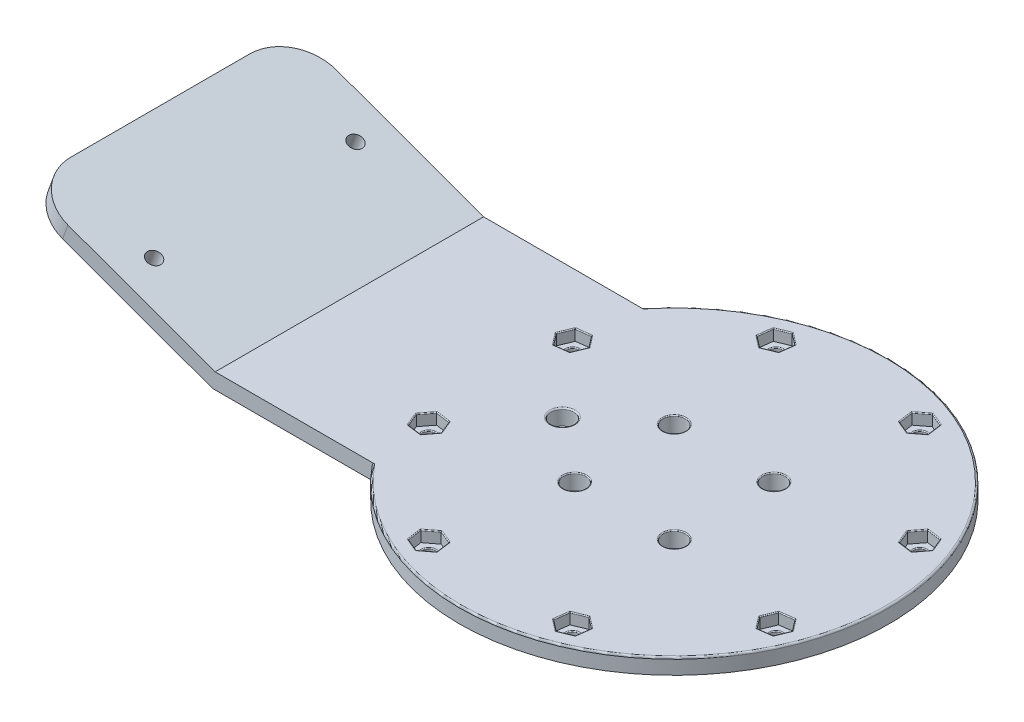
SolidWorks part; units mm, degrees
ref_plane "前视基准面" through (0, 0, 0) normal (0, 0, 1) x (1, 0, 0)
ref_plane "上视基准面" through (0, 0, 0) normal (0, 1, 0) x (1, 0, 0)
ref_plane "右视基准面" through (0, 0, 0) normal (1, 0, 0) x (0, 0, -1)
other "Configuration Table"
sketch "草图1" plane through (0, 0, 0) normal (0, 0, 1) x (1, 0, 0)
  line L0 (48, 6) -> (0, 6)
  line L1 (0, 6) -> (0, 0)
  line L2 (0, 0) -> (48, 0)
  line L3 (48, 0) -> (48, 6)
  line L4 (0, 6) -> (0, 0) construction
revolve "旋转1" add sketch "草图1" angle 360 about L4 reverse direction yes
sketch "草图2" plane through (0, 6, 0) normal (0, 1, 0) x (-1, 0, 0)
  line L0 (42.0084, 15.6507) -> (40.7712, 18.6377)
  line L1 (40.7712, 18.6377) -> (37.5657, 19.0598)
  line L2 (37.5657, 19.0598) -> (35.5974, 16.4947)
  line L3 (35.5974, 16.4947) -> (36.8347, 13.5077)
  line L4 (36.8347, 13.5077) -> (40.0402, 13.0857)
  line L5 (40.0402, 13.0857) -> (42.0084, 15.6507)
extrude "切除-拉伸1" cut sketch "草图2" against normal blind 2.5
sketch "草图3" plane through (0, 6, 0) normal (0, 1, 0) x (-1, 0, 0)
  line L0 (18.6377, 40.7712) -> (15.6507, 42.0084)
  line L1 (15.6507, 42.0084) -> (13.0857, 40.0402)
  line L2 (13.0857, 40.0402) -> (13.5077, 36.8347)
  line L3 (13.5077, 36.8347) -> (16.4947, 35.5974)
  line L4 (16.4947, 35.5974) -> (19.0598, 37.5657)
  line L5 (19.0598, 37.5657) -> (18.6377, 40.7712)
extrude "切除-拉伸2" cut sketch "草图3" against normal blind 2.5
sketch "草图4" plane through (0, 6, 0) normal (0, 1, 0) x (-1, 0, 0)
  line L0 (-15.6507, 42.0084) -> (-18.6377, 40.7712)
  line L1 (-18.6377, 40.7712) -> (-19.0598, 37.5657)
  line L2 (-19.0598, 37.5657) -> (-16.4947, 35.5974)
  line L3 (-16.4947, 35.5974) -> (-13.5077, 36.8347)
  line L4 (-13.5077, 36.8347) -> (-13.0857, 40.0402)
  line L5 (-13.0857, 40.0402) -> (-15.6507, 42.0084)
extrude "切除-拉伸3" cut sketch "草图4" against normal blind 2.5
sketch "草图5" plane through (0, 6, 0) normal (0, 1, 0) x (-1, 0, 0)
  line L0 (-40.7712, 18.6377) -> (-42.0084, 15.6507)
  line L1 (-42.0084, 15.6507) -> (-40.0402, 13.0857)
  line L2 (-40.0402, 13.0857) -> (-36.8347, 13.5077)
  line L3 (-36.8347, 13.5077) -> (-35.5974, 16.4947)
  line L4 (-35.5974, 16.4947) -> (-37.5657, 19.0598)
  line L5 (-37.5657, 19.0598) -> (-40.7712, 18.6377)
extrude "切除-拉伸4" cut sketch "草图5" against normal blind 2.5
sketch "草图6" plane through (0, 6, 0) normal (0, 1, 0) x (-1, 0, 0)
  line L0 (-42.0084, -15.6507) -> (-40.7712, -18.6377)
  line L1 (-40.7712, -18.6377) -> (-37.5657, -19.0598)
  line L2 (-37.5657, -19.0598) -> (-35.5974, -16.4947)
  line L3 (-35.5974, -16.4947) -> (-36.8347, -13.5077)
  line L4 (-36.8347, -13.5077) -> (-40.0402, -13.0857)
  line L5 (-40.0402, -13.0857) -> (-42.0084, -15.6507)
extrude "切除-拉伸5" cut sketch "草图6" against normal blind 2.5
sketch "草图7" plane through (0, 6, 0) normal (0, 1, 0) x (-1, 0, 0)
  line L0 (-18.6377, -40.7712) -> (-15.6507, -42.0084)
  line L1 (-15.6507, -42.0084) -> (-13.0857, -40.0402)
  line L2 (-13.0857, -40.0402) -> (-13.5077, -36.8347)
  line L3 (-13.5077, -36.8347) -> (-16.4947, -35.5974)
  line L4 (-16.4947, -35.5974) -> (-19.0598, -37.5657)
  line L5 (-19.0598, -37.5657) -> (-18.6377, -40.7712)
extrude "切除-拉伸6" cut sketch "草图7" against normal blind 2.5
sketch "草图8" plane through (0, 6, 0) normal (0, 1, 0) x (-1, 0, 0)
  line L0 (15.6507, -42.0084) -> (18.6377, -40.7712)
  line L1 (18.6377, -40.7712) -> (19.0598, -37.5657)
  line L2 (19.0598, -37.5657) -> (16.4947, -35.5974)
  line L3 (16.4947, -35.5974) -> (13.5077, -36.8347)
  line L4 (13.5077, -36.8347) -> (13.0857, -40.0402)
  line L5 (13.0857, -40.0402) -> (15.6507, -42.0084)
extrude "切除-拉伸7" cut sketch "草图8" against normal blind 2.5
sketch "草图9" plane through (0, 6, 0) normal (0, 1, 0) x (-1, 0, 0)
  line L0 (40.7712, -18.6377) -> (42.0084, -15.6507)
  line L1 (42.0084, -15.6507) -> (40.0402, -13.0857)
  line L2 (40.0402, -13.0857) -> (36.8347, -13.5077)
  line L3 (36.8347, -13.5077) -> (35.5974, -16.4947)
  line L4 (35.5974, -16.4947) -> (37.5657, -19.0598)
  line L5 (37.5657, -19.0598) -> (40.7712, -18.6377)
extrude "切除-拉伸8" cut sketch "草图9" against normal blind 2.5
hole_wizard "Ø5.0 (5) 直径孔1" positions "草图11" profile "草图10" hole size "Ø5.0" standard "ANSI Metric"
sketch "草图11" plane through (0, 6, 0) normal (0, 1, 0) x (1, 0, 0)
  point P0 (11.1369, 11.1369)
  point P1 (11.1369, -11.1369)
  point P2 (-11.1369, -11.1369)
  point P3 (-11.1369, 11.1369)
sketch "草图10" plane through (11.1369, 6, -11.1369) normal (1, 0, 0) x (0, 0, 1)
  line L0 (0, 0) -> (0, 6)
  line L1 (0, 6) -> (2.5, 6)
  line L2 (2.5, 6) -> (2.5, 0)
  line L5 (2.5, 0) -> (0, 0)
  line L11 (0, -6.35) -> (0, 107.95) construction
  dimension "通孔孔直径" = 5
  dimension "通孔孔深度" = 6
hole_wizard "Ø3.0 (3) 直径孔1" positions "草图13" profile "草图12" hole size "Ø3.0" standard "ANSI Metric"
sketch "草图13" plane through (0, 3.5, 0) normal (0, 1, 0) x (1, 0, 0)
  point P0 (-38.8029, -16.0727)
  point P1 (-16.0727, -38.8029)
  point P2 (16.0727, -38.8029)
  point P3 (38.8029, -16.0727)
  point P4 (38.8029, 16.0727)
  point P5 (16.0727, 38.8029)
  point P6 (-16.0727, 38.8029)
  point P7 (-38.8029, 16.0727)
sketch "草图12" plane through (-38.8029, 3.5, 16.0727) normal (1, 0, 0) x (0, 0, 1)
  line L0 (0, 0) -> (0, 3.5)
  line L1 (0, 3.5) -> (1.5, 3.5)
  line L2 (1.5, 3.5) -> (1.5, 0)
  line L5 (1.5, 0) -> (0, 0)
  line L11 (0, -6.35) -> (0, 107.95) construction
  dimension "通孔孔直径" = 3
  dimension "通孔孔深度" = 3.5
hole_wizard "Ø5.1 (5.1) 直径孔1" positions "草图15" profile "草图14" hole size "Ø5.1" standard "ANSI Metric"
sketch "草图15" plane through (0, 6, 0) normal (0, 1, 0) x (1, 0, 0)
  point P0 (-25, 0)
sketch "草图14" plane through (-25, 6, 0) normal (1, 0, 0) x (0, 0, 1)
  line L0 (0, 0) -> (0, 3.5)
  line L1 (0, 3.5) -> (2.55, 3.5)
  line L2 (2.55, 3.5) -> (2.55, 0)
  line L5 (2.55, 0) -> (0, 0)
  line L10 (0, 3.5) -> (-2.55, 3.5) construction
  line L11 (0, -6.35) -> (0, 107.95) construction
  dimension "孔直径" = 5.1
  dimension "孔深度" = 3.5
  dimension "导头角度" = 180
fillet "圆角1" radius 0.2 60 edges at (-41.3898, 6, -17.1442) (-41.0243, 6, -14.3682) (-39.1684, 6, -18.8487) (-38.4375, 6, -13.2967) (-36.5816, 6, -17.7772) (-36.2161, 6, -15.0012) (18.8487, 6, -39.1684) (17.1442, 6, -41.3898) (17.7772, 6, -36.5816) (14.3682, 6, -41.0243) (15.0012, 6, -36.2161) (13.2967, 6, -38.4375) (-36.5816, 6, 17.7772) (-39.1684, 6, 18.8487) (-36.2161, 6, 15.0012) (-41.3898, 6, 17.1442) (-38.4375, 6, 13.2967) (-41.0243, 6, 14.3682) (-16.0727, 3.5, -37.3029) (-17.1442, 6, -41.3898) (-18.8487, 6, -39.1684) (-14.3682, 6, -41.0243) (-17.7772, 6, -36.5816) (-13.2967, 6, -38.4375) (-15.0012, 6, -36.2161) (-38.8029, 3.5, 17.5727) (41.3898, 6, -17.1442) (39.1684, 6, -18.8487) (41.0243, 6, -14.3682) (36.5816, 6, -17.7772) (38.4375, 6, -13.2967) (36.2161, 6, -15.0012) (-13.2967, 6, 38.4375) (-14.3682, 6, 41.0243) (-15.0012, 6, 36.2161) (-17.1442, 6, 41.3898) (-17.7772, 6, 36.5816) (-18.8487, 6, 39.1684) (16.0727, 3.5, 40.3029) (17.7772, 6, 36.5816) (18.8487, 6, 39.1684) (15.0012, 6, 36.2161) (17.1442, 6, 41.3898) (13.2967, 6, 38.4375) (14.3682, 6, 41.0243) (38.4375, 6, 13.2967) (41.0243, 6, 14.3682) (36.2161, 6, 15.0012) (41.3898, 6, 17.1442) (36.5816, 6, 17.7772) (39.1684, 6, 18.8487) (-16.0727, 3.5, 40.3029) (16.0727, 3.5, -37.3029) (-11.1369, 6, 13.6369) (11.1369, 6, -8.6369) (-38.8029, 3.5, -14.5727) (11.1369, 6, 13.6369) (38.8029, 3.5, 17.5727) (-11.1369, 6, -8.6369) (38.8029, 3.5, -14.5727) tangent propagation no
fillet "圆角2" radius 0.3 1 edges at (-25, 6, 2.55) tangent propagation no
fillet "圆角3" radius 0.4 1 edges at (0, 6, -48) tangent propagation no
sketch "草图16" plane through (0, 0, 0) normal (0, -1, 0) x (1, 0, 0)
  circle A0 centre (0, 0) radius 48
extrude "切除-拉伸9" cut sketch "草图16" against normal blind 2.5
sketch "草图17" plane through (0, 6, 0) normal (0, 1, 0) x (1, 0, 0)
  line L0 (0, 0) -> (-47.6, 0) construction
  line L1 (-36.9562, 30) -> (-72.6, 30)
  line L2 (-72.6, 30) -> (-72.6, -30)
  line L3 (-36.9562, -30) -> (-72.6, -30)
  circle A0 centre (0, 0) radius 47.6 construction
  arc A1 (-36.9562, 30) -> (-36.9562, -30) centre (0, 0) ccw
  point P8 (0, 0)
  point P9 (0, 0)
  point P11 (0, 0)
  point P13 (-72.6, 0)
  point P14 (-81.3556, 0)
  point P15 (0, 0)
  dimension "D1" = 25
  dimension "D2" = 30
extrude "凸台-拉伸1" add sketch "草图17" against normal blind 3.5
sketch "草图18" plane through (0, 0, -30) normal (0, 0, -1) x (-1, 0, 0)
  line L0 (72.6, 6) -> (114.8862, 21.3909)
  line L1 (114.8862, 21.3909) -> (116.0832, 18.102)
  line L2 (116.0832, 18.102) -> (73.2171, 2.5)
  line L3 (73.2171, 2.5) -> (72.6, 2.5)
  line L4 (72.6, 2.5) -> (72.6, 6)
  point P3 (0, 0)
  dimension "D1" = 20
  dimension "D2" = 45
  dimension "D3" = 3.5
extrude "凸台-拉伸2" add sketch "草图18" against normal up to surface (60 mm away) up to face at (-51.2828, 4.4346, 30)
sketch "草图19" plane through (-6.5642, -18.0351, 0) normal (0.342, 0.9397, 0) x (0.9397, -0.342, 0)
  line L0 (-92.7738, 30) -> (-92.7738, -30) construction
  line L1 (-115.2738, 30) -> (-70.2738, 30) construction
  line L2 (-115.2738, -30) -> (-70.2738, -30) construction
  line L3 (-115.2738, 0) -> (-70.2738, 0) construction
  line L4 (-115.2738, -30) -> (-115.2738, 30) construction
  line L5 (-70.2738, 30) -> (-70.2738, -30) construction
  circle A0 centre (-92.7738, 22.5) radius 1.575
  circle A1 centre (-92.7738, -22.5) radius 1.575
  dimension "D1" = 3.15
  dimension "D2" = 45
extrude "切除-拉伸10" cut sketch "草图19" against normal up to surface (3.5 mm away) up to face at (-94.6502, 10.301, 0)
fillet "圆角4" radius 10 2 edges at (-115.4847, 19.7464, 30) (-115.4847, 19.7464, -30)
